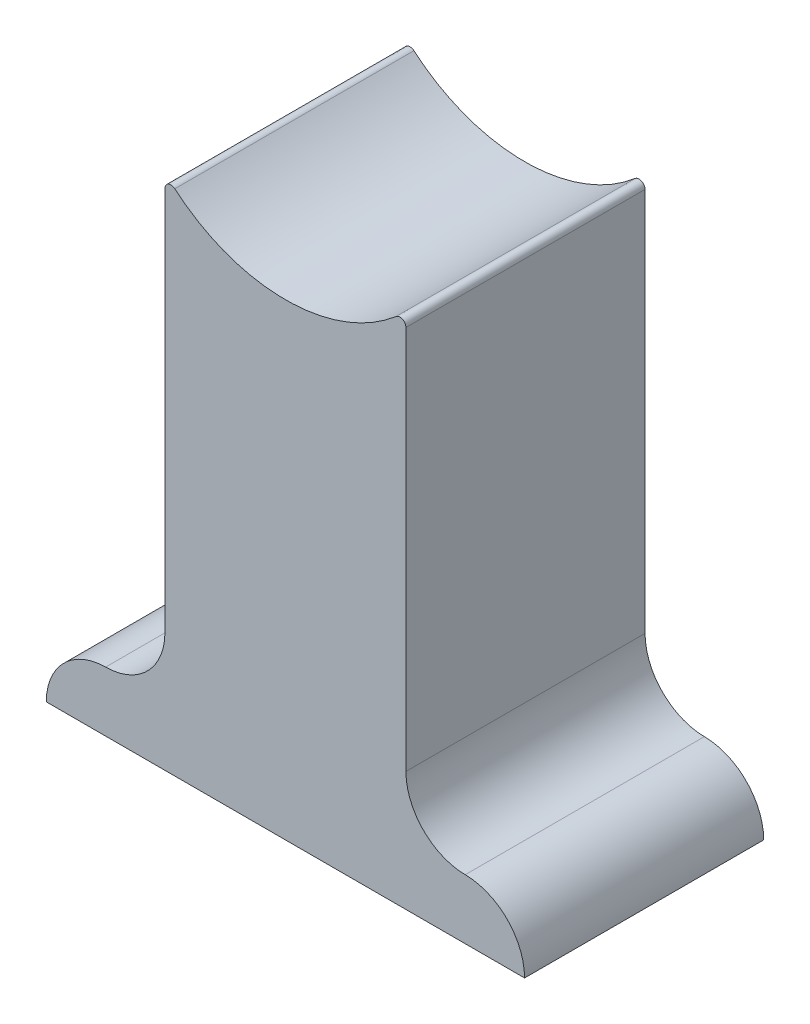
SolidWorks part; units mm, degrees
ref_plane "前视基准面" through (0, 0, 0) normal (0, 0, 1) x (1, 0, 0)
ref_plane "上视基准面" through (0, 0, 0) normal (0, 1, 0) x (1, 0, 0)
ref_plane "右视基准面" through (0, 0, 0) normal (1, 0, 0) x (0, 0, -1)
other "Configuration Table"
sketch "草图1" plane through (0, 0, 0) normal (0, 0, 1) x (1, 0, 0)
  line L0 (0, 41.9453) -> (0, -106.75) construction
  line L1 (-40, -106.75) -> (40, -106.75)
  line L4 (-20.1525, -20.1525) -> (-20.1525, -96.75)
  line L5 (20.1525, -20.1525) -> (20.1525, -96.75)
  line L6 (-40, -106.75) -> (-40, -96.75)
  line L7 (-40, -96.75) -> (-20.1525, -96.75)
  line L8 (40, -96.75) -> (40, -106.75)
  line L9 (20.1525, -96.75) -> (40, -96.75)
  arc A0 (-20.1525, -20.1525) -> (20.1525, -20.1525) centre (0, 0) ccw
  dimension "D1" = 57
  dimension "D2" = 106.75
  dimension "D3" = 40
  dimension "D4" = 80
  dimension "D5" = 10
extrude "凸台-拉伸1" add sketch "草图1" along normal blind 40
fillet "圆角1" radius 1 2 edges at (20.1525, -20.1525, 20) (-20.1525, -20.1525, 20)
fillet "圆角2" radius 10 2 edges at (40, -96.75, 20) (-40, -96.75, 20)
fillet "圆角3" radius 10 2 edges at (20.1525, -96.75, 20) (-20.1525, -96.75, 20)
shell "抽壳1" thickness 1 removed face at (0, -106.75, 20)
